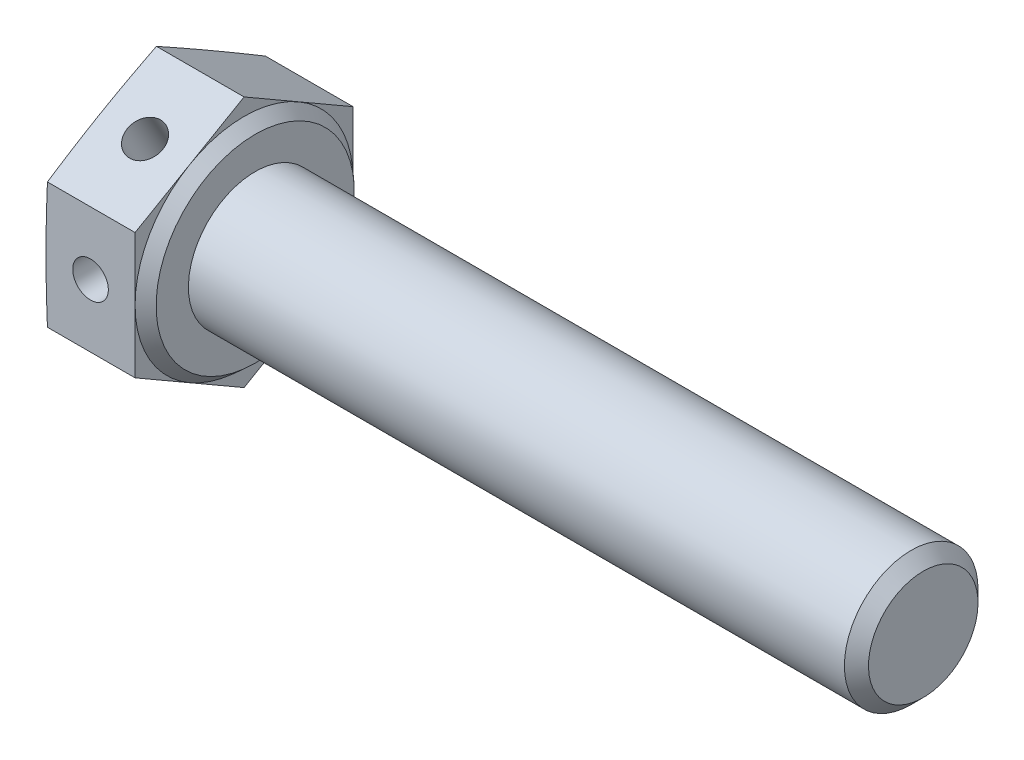
SolidWorks part; units mm, degrees
ref_plane "Front" through (0, 0, 0) normal (0, 0, 1) x (1, 0, 0)
ref_plane "Top" through (0, 0, 0) normal (0, 1, 0) x (1, 0, 0)
ref_plane "Right" through (0, 0, 0) normal (1, 0, 0) x (0, 0, -1)
sketch "Sketch-BaseHead" plane through (0, 0, 0) normal (1, 0, 0) x (0, 0, -1)
  line L1 (0, -5.6523) -> (4.895, -2.8261)
  line L2 (4.895, -2.8261) -> (4.895, 2.8261)
  line L3 (4.895, 2.8261) -> (0, 5.6523)
  line L4 (0, 5.6523) -> (-4.895, 2.8261)
  line L5 (-4.895, 2.8261) -> (-4.895, -2.8261)
  line L6 (-4.895, -2.8261) -> (0, -5.6523)
  circle A0 centre (0, 0) radius 4.895 construction
extrude "BaseHead" add sketch "Sketch-BaseHead" along normal blind 4
sketch "Sketch4" plane through (-0.2646, -5.9169, 0) normal (0, 0, 1) x (0, 1, 0)
  line L0 (5.9169, 3.7369) -> (5.9169, -10.4477) construction
  line L2 (11.5692, -0.2646) -> (10.8119, -0.2646)
  line L4 (10.8119, -0.2646) -> (11.5692, -0.3295)
  line L6 (11.5692, -0.3295) -> (11.5692, -0.2646)
  dimension "D1" = 4.895
  dimension "D2" = 9.79
revolve "HeadChamfer" cut sketch "Sketch4" angle 360 about L0
sketch "Sketch2" plane through (0, 0, 0) normal (0, 1, 0) x (1, 0, 0)
  line L0 (4, 0) -> (4.5, 0)
  line L1 (4.5, 0) -> (4.5, 4.45)
  line L2 (4.5, 4.45) -> (4, 4.895)
  line L3 (4, 4.895) -> (4, 0)
  line L4 (4, 4.895) -> (4, 0) construction
  dimension "D1" = 4.895
  dimension "D2" = 4.45
revolve "Revolve1" add sketch "Sketch2" angle 360 about axis through (-4.0016, 0, 0) along (1, 0, 0)
ref_plane "Plane2" through (19.5, 0, 0) normal (1, 0, 0) x (0, 0, -1)
sketch "Sketch3" plane through (4.5, 0, 0) normal (1, 0, 0) x (0, 0, -1)
  circle A0 centre (0, 0) radius 3
extrude "BaseBody" add sketch "Sketch3" along normal blind 30
cosmetic thread "ThreadCosmetic1" [suppressed] parameters "b"=15, "D2"=4.917
chamfer "Chamfer1" distance 0.5415 angle 45 1 edges at (34.5, 3, 0)
fillet "HeadFillet" [suppressed] radius 0.25
sketch "Sketch5" plane through (0, 0, 0) normal (0, 0, 1) x (1, 0, 0)
  line L1 (4, -4.2392) -> (4, -5.6523) construction
  line L2 (-4.0016, 0) -> (10.1831, 0) construction
  circle A0 centre (2, 0) radius 0.8
  dimension "d1" = 1.6
  dimension "h" = 2
extrude "Hole" cut sketch "Sketch5" against normal through all and the other way through all
pattern_circular "CirPattern1" count 2 over 60 about axis through (34.5, 0, 0) along (-1, 0, 0) of "Hole"
sketch "Sketch6" plane through (0, 0, 0) normal (0, 0, 1) x (1, 0, 0)
  line L0 (33.416, 3.2) -> (33.9575, 3.2)
  line L1 (33.9575, 3.2) -> (33.9575, 3)
  line L2 (33.9575, 3) -> (33.6867, 2.531)
  line L3 (33.416, 3) -> (33.6867, 2.531)
  line L4 (33.416, 3.2) -> (33.416, 3)
  line L5 (34.549, 0) -> (0, 0) construction
  line L6 (33.416, 3) -> (33.9575, 3) construction
  line L7 (33.6867, 3) -> (33.6867, 2.531) construction
  line L8 (33.9585, 3) -> (4.5, 3) construction
  point P5 (33.6867, 3.2)
  dimension "D2" = 0.5415
revolve "Cut-Revolve10" [suppressed] cut sketch "Sketch6" angle 360 about L5
pattern_linear "LPattern10" [suppressed] count 23 spacing 0.6498 of bodies 111
equation "\"D1@Sketch4\" = \"s@Sketch-BaseHead\"/ 2 "
equation "\"D2@Sketch4\" = \"s@Sketch-BaseHead\""
equation "\"D1@Chamfer1\" =  ( \"d@Sketch3\" - \"D2@ThreadCosmetic1\" ) / 2 "
equation "\"b@ThreadCosmetic1\" = \"l@BaseBody\" - \"lg@Plane2\""
equation "\"D1@Sketch2\"=\"s@Sketch-BaseHead\"/2"
equation "\"D2@Sketch6\" = (  \"d@Sketch3\" - \"D2@ThreadCosmetic1\" )  / 2"
equation "\"D3@LPattern10\" = \"D2@Sketch6\" * 1.2"
equation "\"D1@LPattern10\" = \"b@ThreadCosmetic1\" / \"D3@LPattern10\""
